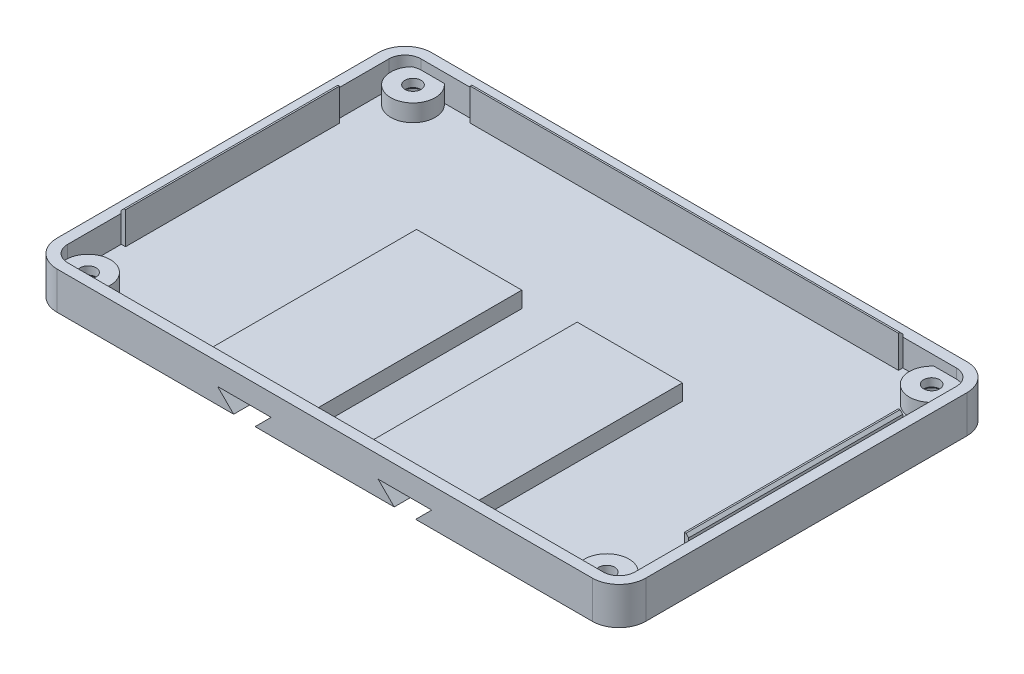
SolidWorks part; units mm, degrees
ref_plane "Front Plane" through (0, 0, 0) normal (0, 0, 1) x (1, 0, 0)
ref_plane "Top Plane" through (0, 0, 0) normal (0, 1, 0) x (1, 0, 0)
ref_plane "Right Plane" through (0, 0, 0) normal (1, 0, 0) x (0, 0, -1)
sketch "Sketch1" plane through (0, 0, 0) normal (0, 1, 0) x (1, 0, 0)
  line L1 (0, 0) -> (110, 0)
  line L2 (0, 0) -> (0, 70)
  line L3 (0, 70) -> (110, 70)
  line L4 (110, 0) -> (110, 70)
  dimension "D1" = 110
  dimension "D2" = 70
extrude "Boss-Extrude1" add sketch "Sketch1" along normal blind 7
fillet "Fillet1" radius 5 4 edges at (0, 3.5, -70) (110, 3.5, -70) (110, 3.5, 0) (0, 3.5, 0)
sketch "Sketch3" plane through (0, 0, 0) normal (0, 0, 1) x (1, 0, 0)
  line L0 (38, 0) -> (35, 3)
  line L1 (5, 0) -> (105, 0) construction
  line L2 (35, 3) -> (45, 3)
  line L3 (45, 3) -> (42, 0)
  line L4 (42, 0) -> (38, 0)
  line L5 (68, 0) -> (65, 3)
  line L6 (65, 3) -> (75, 3)
  line L7 (75, 3) -> (72, 0)
  line L8 (72, 0) -> (68, 0)
  line L9 (45, 3) -> (55, 3) construction
  line L10 (55, 3) -> (65, 3) construction
  line L11 (35, 0) -> (38, 0) construction
  line L12 (45, 0) -> (42, 0) construction
  line L13 (65, 0) -> (68, 0) construction
  line L15 (75, 0) -> (72, 0) construction
  line L16 (5, 7) -> (105, 7) construction
  line L17 (35, 0) -> (35, 3) construction
  point P15 (40, 3)
  point P18 (55, 7)
  point P19 (70, 3)
  dimension "D1" = 3
  dimension "D2" = 10
  dimension "D3" = 30
extrude "Cut-Extrude1" cut sketch "Sketch3" against normal blind 40
shell "Shell1" thickness 2 removed face at (55, 7, -35)
sketch "Sketch2" plane through (0, 2, 0) normal (0, 1, 0) x (1, 0, 0)
  line L0 (105, 68) -> (5, 68) construction
  line L1 (15, 67.2) -> (95, 67.2)
  line L2 (15, 67.2) -> (15, 68)
  line L3 (15, 68) -> (95, 68)
  line L4 (95, 67.2) -> (95, 68)
  line L5 (108, 5) -> (108, 65) construction
  line L6 (108, 55) -> (107.2, 55)
  line L7 (108, 55) -> (108, 15)
  line L8 (108, 15) -> (107.2, 15)
  line L9 (107.2, 55) -> (107.2, 15)
  line L15 (2, 65) -> (2, 5) construction
  line L16 (2, 15) -> (2.8, 15)
  line L17 (2, 15) -> (2, 55)
  line L18 (2, 55) -> (2.8, 55)
  line L19 (2.8, 15) -> (2.8, 55)
  line L20 (2, 65) -> (2, 55) construction
  line L21 (15, 68) -> (5, 68) construction
  line L22 (2, 5) -> (2, 15) construction
  line L23 (5, 2) -> (15, 2) construction
  line L25 (108, 5) -> (108, 15) construction
  line L26 (108, 65) -> (108, 55) construction
  line L27 (105, 68) -> (95, 68) construction
  dimension "D1" = 0.8
  dimension "D2" = 40
  dimension "D3" = 10
extrude "Boss-Extrude2" add sketch "Sketch2" along normal blind 6
chamfer "Chamfer1" distance 0.5 angle 45 3 edges at (55, 8, -68) (108, 8, -35) (2, 8, -35)
sketch "Sketch8" plane through (0, 2, 0) normal (0, 1, 0) x (1, 0, 0)
  line L1 (5, 0) -> (105, 0) construction
  circle A0 centre (103.55, 64.85) radius 4.15
  circle A1 centre (6.65, 64.85) radius 4.15
  circle A2 centre (6.65, 4.15) radius 4.15
  circle A3 centre (6.65, 4.15) radius 1.2 construction
  circle A4 centre (103.55, 4.15) radius 4.15
  circle A5 centre (103.55, 4.15) radius 1.2 construction
extrude "Boss-Extrude3" add sketch "Sketch8" along normal offset from surface (3.2 mm away) 1.8 up to face at (55, 7, -35)
sketch "Sketch9" plane through (0, 5.2, 0) normal (0, 1, 0) x (1, 0, 0)
  circle A0 centre (6.65, 64.85) radius 1.5
  circle A1 centre (6.65, 4.15) radius 1.5
  circle A2 centre (103.55, 4.15) radius 1.5
  circle A3 centre (103.55, 64.85) radius 1.5
  arc A4 (107.6668, 3.6258) -> (100.0004, 2) centre (103.55, 4.15) ccw construction
  arc A5 (100.8481, 68) -> (106.859, 67.3546) centre (103.55, 64.85) ccw construction
  arc A6 (3.5804, 67.6429) -> (9.3519, 68) centre (6.65, 64.85) ccw construction
  arc A7 (10.1996, 2) -> (2.6149, 3.1803) centre (6.65, 4.15) ccw construction
  dimension "D1" = 3
extrude "Cut-Extrude5" cut sketch "Sketch9" against normal through all both and the other way through all
sketch "Sketch10" plane through (0, 0, 0) normal (0, -1, 0) x (-1, 0, 0)
  circle A0 centre (-6.65, 4.15) radius 3
  circle A1 centre (-6.65, 64.85) radius 3
  circle A2 centre (-103.55, 64.85) radius 3
  circle A3 centre (-103.55, 4.15) radius 3
  dimension "D1" = 6
extrude "Cut-Extrude6" cut sketch "Sketch10" against normal offset from surface (3.2 mm away) 2 up to face at (6.65, 5.2, -66.35)
chamfer "Chamfer2" distance 0.5 angle 45 8 edges at (103.55, 0, -7.15) (103.55, 3.2, -5.65) (103.55, 0, -67.85) (103.55, 3.2, -66.35) (6.65, 0, -7.15) (6.65, 3.2, -5.65) (6.65, 3.2, -66.35) (6.65, 0, -67.85)
sketch "Sketch11" plane through (0, 0, -42) normal (0, 0, -1) x (-1, 0, 0)
  line L0 (-60.1716, 5) -> (-60.1716, 2)
  line L1 (-60.1716, 2) -> (-63.1716, 2)
  line L2 (-63.1716, 2) -> (-60.1716, 5)
  line L3 (-49.8284, 5) -> (-46.8284, 2)
  line L4 (-46.8284, 2) -> (-49.8284, 2)
  line L5 (-49.8284, 2) -> (-49.8284, 5)
  line L7 (-33.1716, 2) -> (-30.1716, 5)
  line L8 (-30.1716, 5) -> (-30.1716, 2)
  line L9 (-30.1716, 2) -> (-33.1716, 2)
  line L10 (-79.8284, 5) -> (-79.8284, 2)
  line L11 (-79.8284, 2) -> (-76.8284, 2)
  line L12 (-76.8284, 2) -> (-79.8284, 5)
extrude "Boss-Extrude4" add sketch "Sketch11" against normal up to next
